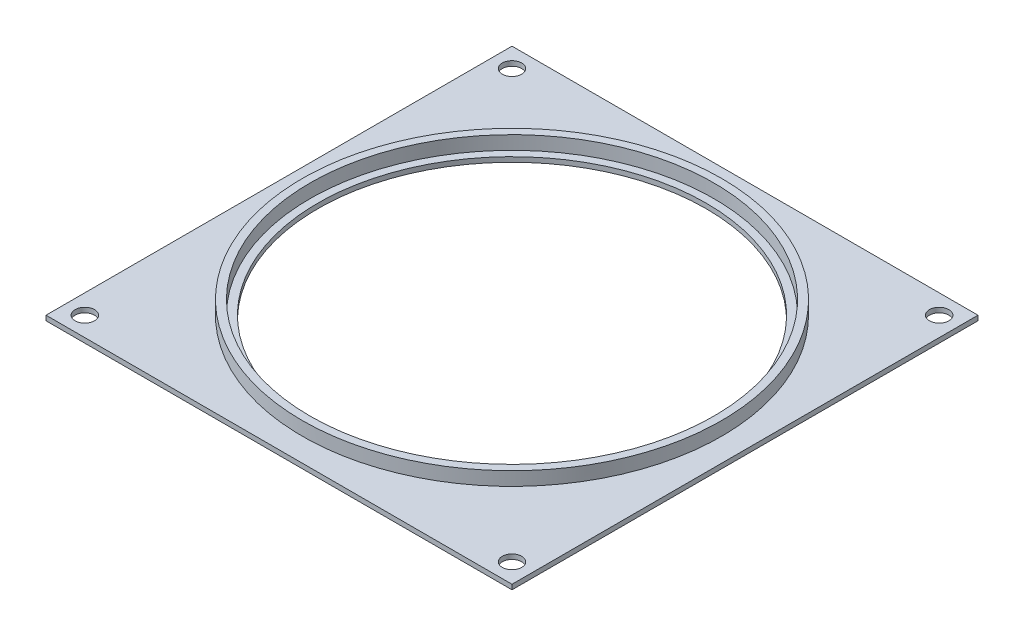
SolidWorks part; units mm, degrees
material "Alloy Steel"
ref_plane "Front Plane" through (0, 0, 0) normal (0, 0, 1) x (1, 0, 0)
ref_plane "Top Plane" through (0, 0, 0) normal (0, 1, 0) x (1, 0, 0)
ref_plane "Right Plane" through (0, 0, 0) normal (1, 0, 0) x (0, 0, -1)
sketch "Sketch1" plane through (0, 0, 0) normal (0, 1, 0) x (1, 0, 0)
  line L1 (-76.2, -76.2) -> (76.2, -76.2)
  line L2 (-76.2, -76.2) -> (-76.2, 76.2)
  line L3 (-76.2, 76.2) -> (76.2, 76.2)
  line L4 (76.2, -76.2) -> (76.2, 76.2)
  line L5 (-76.2, -76.2) -> (76.2, 76.2) construction
  line L6 (-76.2, 76.2) -> (76.2, -76.2) construction
  circle A0 centre (0, 0) radius 63.5
  circle A1 centre (-69.85, 69.85) radius 3.175
  circle A2 centre (69.85, 69.85) radius 3.175
  circle A3 centre (69.85, -69.85) radius 3.175
  circle A4 centre (-69.85, -69.85) radius 3.175
  point P9 (-43.4034, -63.2601)
  point P18 (0, 0)
  dimension "D1" = 127
  dimension "D4" = 6.35
  dimension "D2" = 152.4
  dimension "D3" = 152.4
  dimension "D5" = 6.35
  dimension "D6" = 4
extrude "Boss-Extrude1" add sketch "Sketch1" along normal blind 1.5875
sketch "Sketch2" plane through (0, 1.5875, 0) normal (0, 1, 0) x (1, 0, 0)
  circle A0 centre (0, 0) radius 63.5 construction
  circle A1 centre (0, 0) radius 63.5
  circle A2 centre (0, 0) radius 66.04
  circle A3 centre (0, 0) radius 68.58
  dimension "D1" = 2.54
  dimension "D2" = 2.54
extrude "Boss-Extrude2" add sketch "Sketch2" along normal blind 4.445 contours A3 A2 region at (-66.6403, 1.5875, 0)
